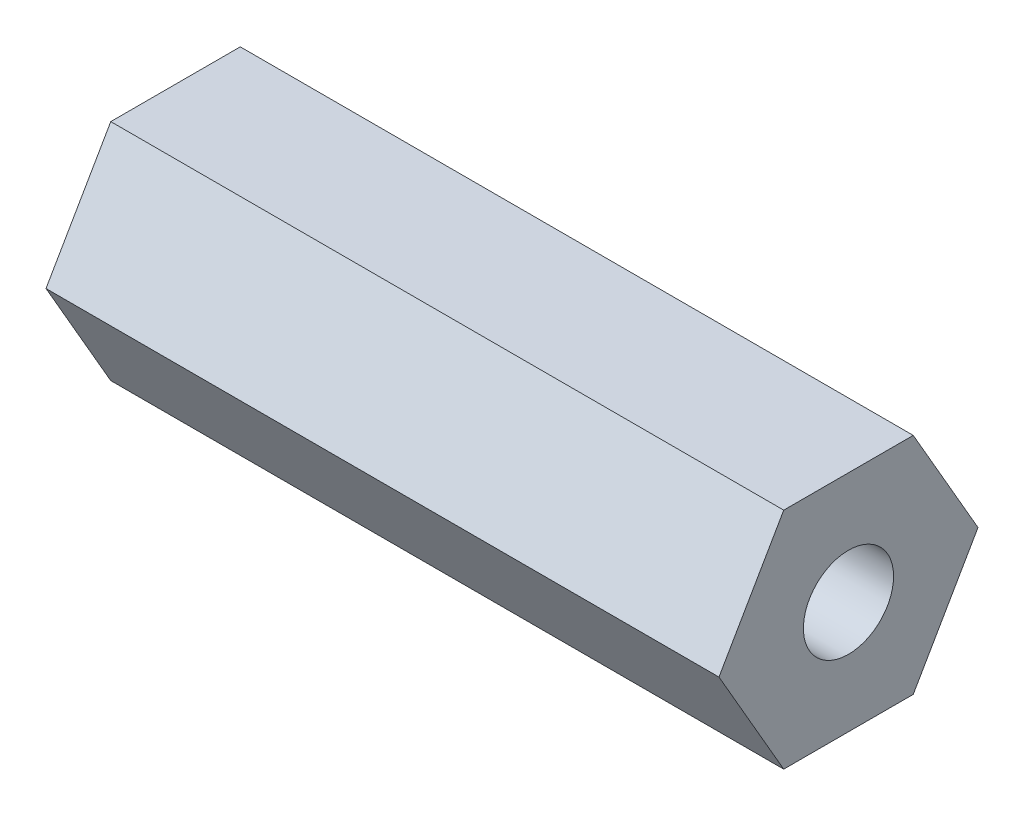
SolidWorks part; units mm, degrees
ref_plane "Front" through (0, 0, 0) normal (0, 0, 1) x (1, 0, 0)
ref_plane "Top" through (0, 0, 0) normal (0, 1, 0) x (1, 0, 0)
ref_plane "Right" through (0, 0, 0) normal (1, 0, 0) x (0, 0, -1)
sketch "Sketch1" plane through (0, 0, 0) normal (1, 0, 0) x (0, 0, -1)
  line L1 (7.3323, 0) -> (3.6662, 6.35)
  line L2 (3.6662, 6.35) -> (-3.6662, 6.35)
  line L3 (-3.6662, 6.35) -> (-7.3323, 0)
  line L4 (-7.3323, 0) -> (-3.6662, -6.35)
  line L5 (-3.6662, -6.35) -> (3.6662, -6.35)
  line L6 (3.6662, -6.35) -> (7.3323, 0)
  circle A0 centre (0, 0) radius 6.35 construction
  dimension "D1" = 12.7
extrude "Boss-Extrude1" add sketch "Sketch1" along normal mid plane 38.1
ref_axis "Axis1" through (-80.9, 0, 0) along (1, 0, 0)
hole_wizard "1/4-20 Tapped Hole1" positions "Sketch2" profile "Sketch3" tap size "1/4-20" standard "ANSI Inch" end condition through all
sketch "Sketch2" plane through (19.05, 0, 0) normal (1, 0, 0) x (0, 0, -1)
  point P0 (0, 0)
sketch "Sketch3" plane through (19.05, 0, 0) normal (0, 1, 0) x (0, 0, -1)
  line L0 (0, 0) -> (0, 38.1)
  line L1 (0, 38.1) -> (2.5527, 38.1)
  line L2 (2.5527, 38.1) -> (2.5527, 0)
  line L5 (2.5527, 0) -> (0, 0)
  line L11 (0, -6.35) -> (0, 107.95) construction
  dimension "Thru Tap Drill Dia." = 5.1054
  dimension "Thru Tap Drill Depth" = 38.1
cosmetic thread "Hole Thread1" parameters "D2"=6.35
